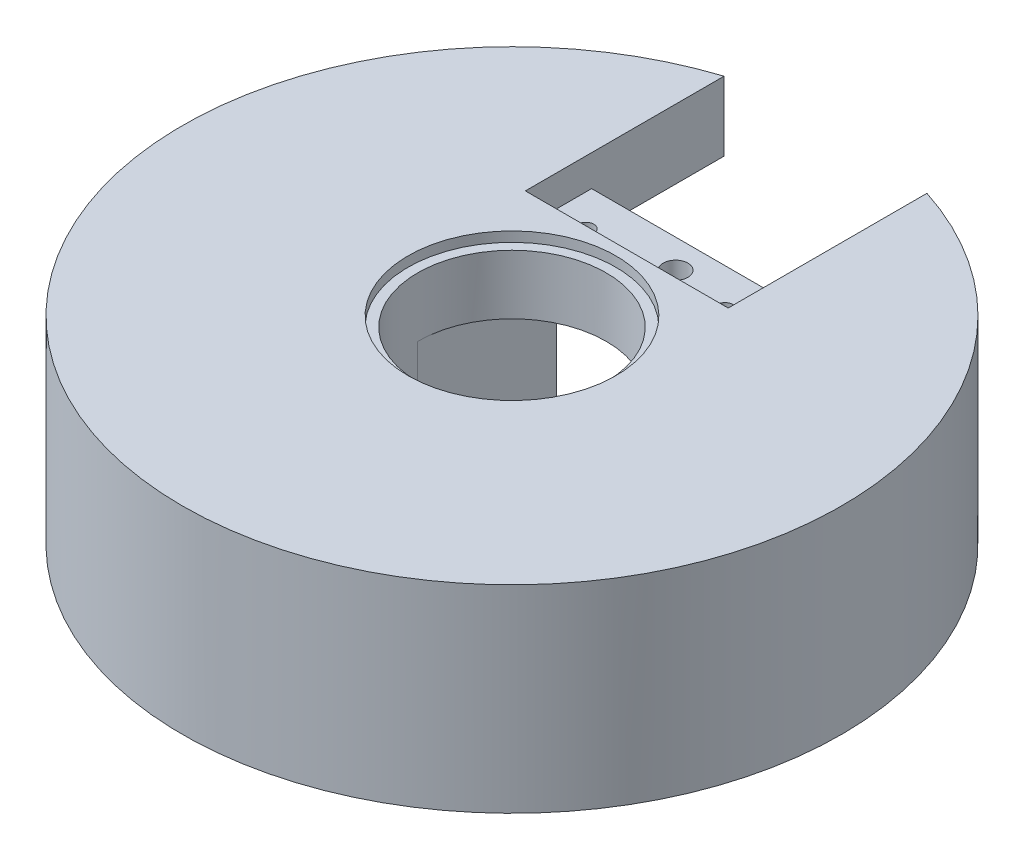
SolidWorks part; units mm, degrees
other "Markup2"
sketch "Sketch11" plane through (-33.3, 0, -31.6832) normal (-0.1985, -0.3048, -0.9315) x (0.9607, 0.1275, -0.2465)
ref_plane "Front Plane" through (0, 0, 0) normal (0, 0, 1) x (1, 0, 0)
ref_plane "Top Plane" through (0, 0, 0) normal (0, 1, 0) x (1, 0, 0)
ref_plane "Right Plane" through (0, 0, 0) normal (1, 0, 0) x (0, 0, -1)
sketch "Sketch1" plane through (0, 0, 0) normal (0, 1, 0) x (1, 0, 0)
  circle A0 centre (0, 0) radius 33.3
  dimension "D1" = 66.6
extrude "Boss-Extrude1" add sketch "Sketch1" along normal blind 20
sketch "Sketch3" plane through (0, 0, 0) normal (0, -1, 0) x (1, 0, 0)
  line L0 (3.2928, 18) -> (-5.3006, 18) construction
  line L1 (2.5019, 18) -> (-2.5019, 18)
  arc A0 (-2.5019, 18) -> (2.5019, 18) centre (0, 18) ccw
  point P10 (0, 0)
  dimension "D1" = 18
revolve "Cut-Revolve7" cut sketch "Sketch3" angle 360 about L0
pattern_circular "CirPattern1" count 3 over 360 about axis through (0, 0, 0) along (0, 1, 0) of "Cut-Revolve7"
sketch "Sketch5" plane through (0, 0, 0) normal (0, -1, 0) x (1, 0, 0)
  line L0 (-9.525, 0) -> (-9.525, -14)
  line L1 (-9.525, -14) -> (-21.2026, -25.6776)
  line L2 (0, -1.8595) -> (0, 3.43) construction
  line L3 (9.525, 0) -> (9.525, -14)
  line L4 (9.525, -14) -> (21.2026, -25.6776)
  circle A0 centre (0, 0) radius 9.525
  circle A3 centre (0, 0) radius 33.3 construction
  circle A4 centre (0, 0) radius 33.3
  circle M5 centre (0, 0) radius 33.3
  dimension "D1" = 19.05
  dimension "D2" = 14
  dimension "D3" = 135
extrude "Cut-Extrude1" cut sketch "Sketch5" against normal blind 13 contours A0 L0 L1 L4 L3 M5 | A0 region at (0, 0, -21.3493) region at (0, 0, 0)
sketch "Sketch6" plane through (0, 20, 0) normal (0, 1, 0) x (1, 0, 0)
  circle A0 centre (0, 0) radius 9.525
  circle A1 centre (0, 0) radius 10.5
  dimension "D1" = 19.05
  dimension "D2" = 21
extrude "Cut-Extrude3" cut sketch "Sketch6" against normal up to next contours A0 region at (0, 20, 0)
extrude "Cut-Extrude4" cut sketch "Sketch6<4>" against normal blind 1 contours A1 A0 region at (-10.203, 20, 0)
sketch "Sketch6<4>" plane through (0, 20, 0) normal (0, 1, 0) x (1, 0, 0) same geometry as "Sketch6"
sketch "Sketch7" plane through (0, 20, 0) normal (0, 1, 0) x (1, 0, 0)
  line L0 (-7.03, 14.5) -> (7.03, 14.5) construction
  circle A0 centre (-7.03, 14.5) radius 0.8
  circle A1 centre (7.03, 14.5) radius 0.8
  circle A2 centre (1.13, 15.4) radius 1.25
  point P4 (0, 14.5)
  dimension "D1" = 1.6
  dimension "D4" = 0.9
  dimension "D6" = 2.5
  dimension "D2" = 14.06
  dimension "D3" = 14.5
  dimension "D5" = 5.9
extrude "Cut-Extrude5" cut sketch "Sketch7" against normal through all
sketch "Sketch8" plane through (0, 20, 0) normal (0, 1, 0) x (1, 0, 0)
  line L1 (-10.25, 11.6) -> (10.25, 11.6)
  line L2 (-10.25, 11.6) -> (-10.25, 36.6)
  line L3 (-10.25, 36.6) -> (10.25, 36.6)
  line L4 (10.25, 11.6) -> (10.25, 36.6)
  line L5 (-10.25, 11.6) -> (10.25, 36.6) construction
  line L6 (-10.25, 36.6) -> (10.25, 11.6) construction
  circle A0 centre (-7.03, 14.5) radius 0.8 construction
  point P0 (0, 24.1)
  point P7 (0, 0)
  dimension "D1" = 25
  dimension "D2" = 20.5
  dimension "D3" = 2.9
extrude "Cut-Extrude6" cut sketch "Sketch8" against normal blind 3.15
sketch "Sketch9" plane through (0, 16.85, 0) normal (0, 1, 0) x (1, 0, 0)
  line L0 (10.25, 11.6) -> (10.25, 31.6832) construction
  line L1 (-10.25, 18.3) -> (10.25, 18.3)
  line L2 (-10.25, 18.3) -> (-10.25, 38.3)
  line L3 (-10.25, 38.3) -> (10.25, 38.3)
  line L4 (10.25, 18.3) -> (10.25, 38.3)
  line L5 (-10.25, 18.3) -> (10.25, 38.3) construction
  line L6 (-10.25, 38.3) -> (10.25, 18.3) construction
  line L7 (-10.25, 31.6832) -> (-10.25, 11.6) construction
  circle A0 centre (-7.03, 14.5) radius 0.8 construction
  point P0 (0, 28.3)
  dimension "D1" = 3.8
  dimension "D2" = 20
extrude "Cut-Extrude7" cut sketch "Sketch9" against normal up to next
